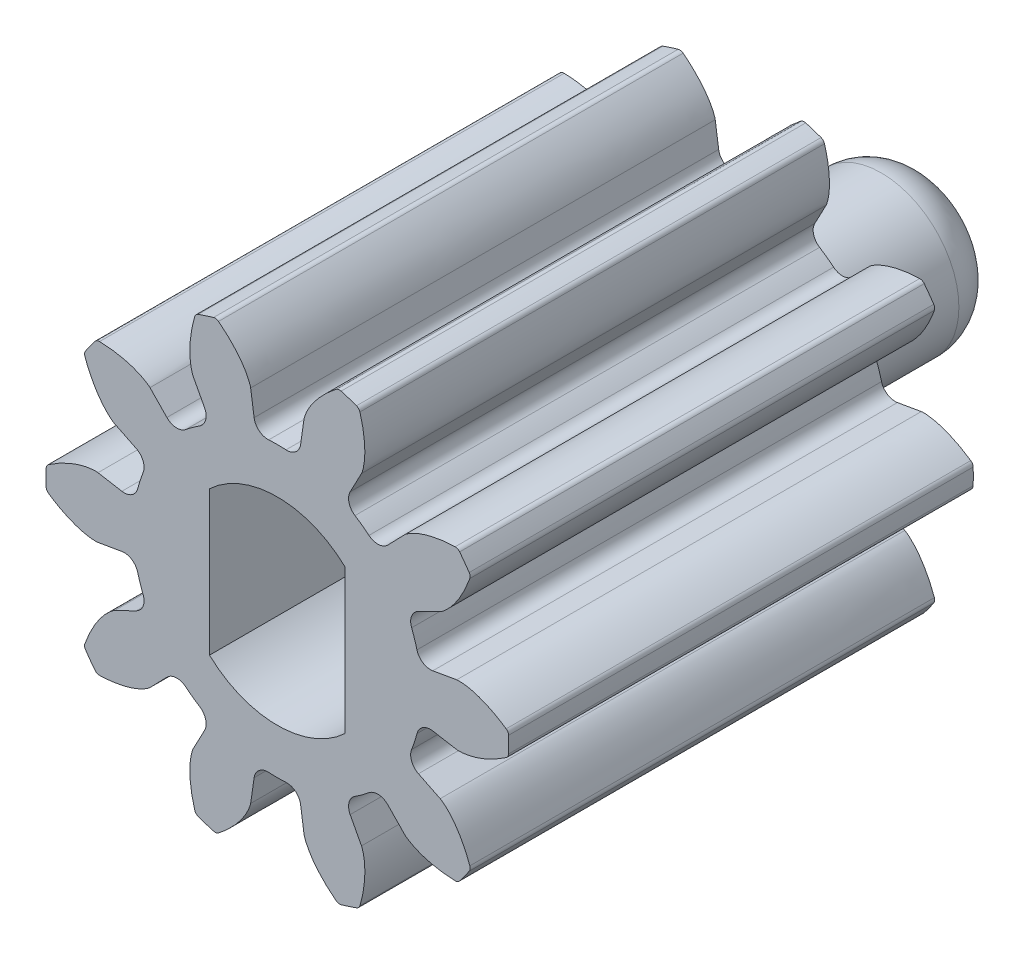
SolidWorks part; units mm, degrees
material "ABS"
ref_plane "Front" through (0, 0, 0) normal (0, 0, 1) x (1, 0, 0)
ref_plane "Top" through (0, 0, 0) normal (0, 1, 0) x (1, 0, 0)
ref_plane "Right" through (0, 0, 0) normal (1, 0, 0) x (0, 0, -1)
sketch "Sketch1" plane through (0, 0, 0) normal (0, 0, 1) x (1, 0, 0)
  circle A0 centre (0, 0) radius 6.35
  dimension "OutsideDiameter" = 12.7
extrude "Boss-Extrude1" add sketch "Sketch1" along normal blind 12.7
sketch "Sketch3" plane through (0, 0, 0) normal (0, 0, 1) x (1, 0, 0)
  line L0 (0, 0) -> (43.7181, 0) construction
  line L2 (0, 0) -> (-0.5624, 3.9287) construction
  line L3 (0, 0) -> (0.5624, 3.9287) construction
  line L4 (0.5624, 3.9287) -> (0.7046, 4.9224) construction
  line L5 (0, 0) -> (0, 61.276) construction
  line L6 (-0.5624, 3.9287) -> (-0.7046, 4.9224) construction
  circle A0 centre (0, 0) radius 6.35 construction
  circle A1 centre (0, 0) radius 5.2917 construction
  circle A2 centre (0, 0) radius 4.9725 construction
  arc A3 (0.5624, 3.9287) -> (-0.5624, 3.9287) centre (0, 0) ccw construction
  arc A5 (1.6642, 6.128) -> (-1.6642, 6.128) centre (0, 0) ccw
  spline S0 degree 4 poles (-0.7046, 4.9224) (-0.705, 4.9247) (-0.7061, 4.9311) (-0.7087, 4.9431) (-0.7137, 4.9626) (-0.721, 4.9872) (-0.7316, 5.0187) (-0.7454, 5.0554) (-0.7621, 5.0953) (-0.7818, 5.1381) (-0.8028, 5.1804) (-0.825, 5.2221) (-0.8483, 5.2631) (-0.8779, 5.3122) (-0.9151, 5.3703) (-0.9613, 5.437) (-1.0167, 5.511) (-1.0764, 5.5846) (-1.1378, 5.6556) (-1.2027, 5.7255) (-1.2676, 5.7919) (-1.338, 5.8588) (-1.4044, 5.9196) (-1.4819, 5.9855) (-1.5453, 6.0379) (-1.6323, 6.1046) (-1.6846, 6.1433) (-1.7469, 6.1876) (-1.7752, 6.2068) (-1.7925, 6.2186) knots 0 0 0 0 0 0.005377 0.015084 0.028532 0.04661 0.064855 0.092111 0.119476 0.146842 0.174209 0.201575 0.228941 0.256307 0.307035 0.361767 0.4165 0.471232 0.525964 0.580697 0.635429 0.690161 0.744894 0.799626 0.854358 0.909091 0.954545 1 1 1 1 1 construction
  spline S1 degree 4 poles (-0.7046, 4.9224) (-0.705, 4.9247) (-0.7061, 4.9311) (-0.7087, 4.9431) (-0.7137, 4.9626) (-0.721, 4.9872) (-0.7316, 5.0187) (-0.7454, 5.0554) (-0.7621, 5.0953) (-0.7818, 5.1381) (-0.8028, 5.1804) (-0.825, 5.2221) (-0.8483, 5.2631) (-0.8779, 5.3122) (-0.9151, 5.3703) (-0.9613, 5.437) (-1.0167, 5.511) (-1.0764, 5.5846) (-1.1378, 5.6556) (-1.2027, 5.7255) (-1.2676, 5.7919) (-1.338, 5.8588) (-1.4044, 5.9196) (-1.4819, 5.9855) (-1.5453, 6.0379) (-1.6134, 6.0902) (-1.647, 6.1153) (-1.6642, 6.128) knots 0 0 0 0 0 0.005377 0.015084 0.028532 0.04661 0.064855 0.092111 0.119476 0.146842 0.174209 0.201575 0.228941 0.256307 0.307035 0.361767 0.4165 0.471232 0.525964 0.580697 0.635429 0.690161 0.744894 0.799626 0.854358 0.909091 0.909091 0.909091 0.909091 0.909091
  spline S2 degree 4 poles (0.7046, 4.9224) (0.705, 4.9247) (0.7061, 4.9311) (0.7087, 4.9431) (0.7137, 4.9626) (0.721, 4.9872) (0.7316, 5.0187) (0.7454, 5.0554) (0.7621, 5.0953) (0.7818, 5.1381) (0.8028, 5.1804) (0.825, 5.2221) (0.8483, 5.2631) (0.8779, 5.3122) (0.9151, 5.3703) (0.9613, 5.437) (1.0167, 5.511) (1.0764, 5.5846) (1.1378, 5.6556) (1.2027, 5.7255) (1.2676, 5.7919) (1.338, 5.8588) (1.4044, 5.9196) (1.4819, 5.9855) (1.5453, 6.0379) (1.6323, 6.1046) (1.6846, 6.1433) (1.7469, 6.1876) (1.7752, 6.2068) (1.7925, 6.2186) knots 0 0 0 0 0 0.005377 0.015084 0.028532 0.04661 0.064855 0.092111 0.119476 0.146842 0.174209 0.201575 0.228941 0.256307 0.307035 0.361767 0.4165 0.471232 0.525964 0.580697 0.635429 0.690161 0.744894 0.799626 0.854358 0.909091 0.954545 1 1 1 1 1 construction
  spline S3 degree 4 poles (0.7046, 4.9224) (0.705, 4.9247) (0.7061, 4.9311) (0.7087, 4.9431) (0.7137, 4.9626) (0.721, 4.9872) (0.7316, 5.0187) (0.7454, 5.0554) (0.7621, 5.0953) (0.7818, 5.1381) (0.8028, 5.1804) (0.825, 5.2221) (0.8483, 5.2631) (0.8779, 5.3122) (0.9151, 5.3703) (0.9613, 5.437) (1.0167, 5.511) (1.0764, 5.5846) (1.1378, 5.6556) (1.2027, 5.7255) (1.2676, 5.7919) (1.338, 5.8588) (1.4044, 5.9196) (1.4819, 5.9855) (1.5453, 6.0379) (1.6134, 6.0902) (1.647, 6.1153) (1.6642, 6.128) knots 0 0 0 0 0 0.005377 0.015084 0.028532 0.04661 0.064855 0.092111 0.119476 0.146842 0.174209 0.201575 0.228941 0.256307 0.307035 0.361767 0.4165 0.471232 0.525964 0.580697 0.635429 0.690161 0.744894 0.799626 0.854358 0.909091 0.909091 0.909091 0.909091 0.909091
  point P0 (0, 3.9688)
  dimension "OutsideDiameter" = 12.7
  dimension "PitchCircle" = 10.5833
  dimension "BaseCircle" = 9.9451
  dimension "DedendumCircle" = 7.9375
sketch "DCLTBC" plane through (0, 0, 0) normal (0, 0, 1) x (1, 0, 0)
  line L0 (0, 0) -> (41.04, 0) construction
  line L1 (-0.5624, 3.9287) -> (-0.7046, 4.9224) construction
  line L2 (0.5624, 3.9287) -> (0.7046, 4.9224) construction
  line L3 (-0.5624, 3.9287) -> (-0.7046, 4.9224)
  line L4 (0.5624, 3.9287) -> (0.7046, 4.9224)
  line L5 (0, 0) -> (0, 104.9356) construction
  circle A0 centre (0, 0) radius 6.35
  circle A1 centre (0, 0) radius 5.2917 construction
  circle A2 centre (0, 0) radius 4.9725 construction
  arc A3 (0.5624, 3.9287) -> (-0.5624, 3.9287) centre (0, 0) ccw construction
  arc A4 (0.5624, 3.9287) -> (-0.5624, 3.9287) centre (0, 0) ccw
  spline S0 degree 4 poles (-988.7588, -149.038) (-11.8151, 2.4708) (-0.7866, 4.3496) (-0.6413, 4.6789) (-0.7137, 4.9626) (-0.721, 4.9872) (-0.7316, 5.0187) (-0.7454, 5.0554) (-0.7621, 5.0953) (-0.7818, 5.1381) (-0.8028, 5.1804) (-0.825, 5.2221) (-0.8483, 5.2631) (-0.8779, 5.3122) (-0.9151, 5.3703) (-0.9613, 5.437) (-1.0167, 5.511) (-1.0764, 5.5846) (-1.1378, 5.6556) (-1.2027, 5.7255) (-1.2676, 5.7919) (-1.338, 5.8588) (-1.4044, 5.9196) (-1.4819, 5.9855) (-1.8387, 6.2805) (-3.231, 7.2231) (17.05, -7.85) (-807.2758, 598.5552) knots -0.632257 -0.632257 -0.632257 -0.632257 -0.632257 0.005377 0.015084 0.028532 0.04661 0.064855 0.092111 0.119476 0.146842 0.174209 0.201575 0.228941 0.256307 0.307035 0.361767 0.4165 0.471232 0.525964 0.580697 0.635429 0.690161 0.744894 0.799626 0.854358 1.920904 1.920904 1.920904 1.920904 1.920904 only from (-0.7046, 4.9224) to (-1.6642, 6.128) construction
  spline S1 degree 4 poles (988.7588, -149.038) (11.8151, 2.4708) (0.7866, 4.3496) (0.6413, 4.6789) (0.7137, 4.9626) (0.721, 4.9872) (0.7316, 5.0187) (0.7454, 5.0554) (0.7621, 5.0953) (0.7818, 5.1381) (0.8028, 5.1804) (0.825, 5.2221) (0.8483, 5.2631) (0.8779, 5.3122) (0.9151, 5.3703) (0.9613, 5.437) (1.0167, 5.511) (1.0764, 5.5846) (1.1378, 5.6556) (1.2027, 5.7255) (1.2676, 5.7919) (1.338, 5.8588) (1.4044, 5.9196) (1.4819, 5.9855) (1.8387, 6.2805) (3.231, 7.2231) (-17.05, -7.85) (807.2758, 598.5552) knots -0.632257 -0.632257 -0.632257 -0.632257 -0.632257 0.005377 0.015084 0.028532 0.04661 0.064855 0.092111 0.119476 0.146842 0.174209 0.201575 0.228941 0.256307 0.307035 0.361767 0.4165 0.471232 0.525964 0.580697 0.635429 0.690161 0.744894 0.799626 0.854358 1.920904 1.920904 1.920904 1.920904 1.920904 only from (0.7046, 4.9224) to (1.6642, 6.128) construction
  spline S2 degree 4 poles (-0.7046, 4.9224) (-0.705, 4.9247) (-0.7061, 4.9311) (-0.7087, 4.9431) (-0.7137, 4.9626) (-0.721, 4.9872) (-0.7316, 5.0187) (-0.7454, 5.0554) (-0.7621, 5.0953) (-0.7818, 5.1381) (-0.8028, 5.1804) (-0.825, 5.2221) (-0.8483, 5.2631) (-0.8779, 5.3122) (-0.9151, 5.3703) (-0.9613, 5.437) (-1.0167, 5.511) (-1.0764, 5.5846) (-1.1378, 5.6556) (-1.2027, 5.7255) (-1.2676, 5.7919) (-1.338, 5.8588) (-1.4044, 5.9196) (-1.4819, 5.9855) (-1.5453, 6.0379) (-1.6134, 6.0902) (-1.647, 6.1153) (-1.6642, 6.128) knots 0 0 0 0 0 0.005377 0.015084 0.028532 0.04661 0.064855 0.092111 0.119476 0.146842 0.174209 0.201575 0.228941 0.256307 0.307035 0.361767 0.4165 0.471232 0.525964 0.580697 0.635429 0.690161 0.744894 0.799626 0.854358 0.909091 0.909091 0.909091 0.909091 0.909091
  spline S3 degree 4 poles (0.7046, 4.9224) (0.705, 4.9247) (0.7061, 4.9311) (0.7087, 4.9431) (0.7137, 4.9626) (0.721, 4.9872) (0.7316, 5.0187) (0.7454, 5.0554) (0.7621, 5.0953) (0.7818, 5.1381) (0.8028, 5.1804) (0.825, 5.2221) (0.8483, 5.2631) (0.8779, 5.3122) (0.9151, 5.3703) (0.9613, 5.437) (1.0167, 5.511) (1.0764, 5.5846) (1.1378, 5.6556) (1.2027, 5.7255) (1.2676, 5.7919) (1.338, 5.8588) (1.4044, 5.9196) (1.4819, 5.9855) (1.5453, 6.0379) (1.6134, 6.0902) (1.647, 6.1153) (1.6642, 6.128) knots 0 0 0 0 0 0.005377 0.015084 0.028532 0.04661 0.064855 0.092111 0.119476 0.146842 0.174209 0.201575 0.228941 0.256307 0.307035 0.361767 0.4165 0.471232 0.525964 0.580697 0.635429 0.690161 0.744894 0.799626 0.854358 0.909091 0.909091 0.909091 0.909091 0.909091
  dimension "OutsideDiameter" = 12.7
  dimension "PitchCircle" = 10.5833
  dimension "BaseCircle" = 9.9451
extrude "Cut-Extrude-DCLTBC" cut sketch "DCLTBC" along normal through all contours L4 S3 A0 S2 L3 A4 region at (0, 5.3543, 0)
fillet "Fillet-Tip-DCLTBC" radius 0.1775 2 edges at (1.6642, 6.128, 6.35) (-1.6642, 6.128, 6.35)
fillet "Fillet-Root-DCLTBC" radius 0.3551 2 edges at (-0.5624, 3.9287, 6.35) (0.5624, 3.9287, 6.35)
pattern_circular "CirPattern-DCLTBC" count 10 over 360 about axis through (0, 0, 12.7) along (0, 0, 1) of "Cut-Extrude-DCLTBC", "Fillet-Tip-DCLTBC", "Fillet-Root-DCLTBC"
sketch "DCGTBC" [suppressed] plane through (0, 0, 0) normal (0, 0, 1) x (1, 0, 0)
  line L0 (0, 0) -> (41.04, 0) construction
  line L1 (-22.6634, 1.9828) -> (0, 0) construction
  line L2 (0, 0) -> (22.6634, 1.9828) construction
  line L3 (0, 0) -> (-16.5124, 0)
  line L5 (0, 0) -> (0, 104.9356) construction
  circle A0 centre (0, 0) radius 25
  circle A1 centre (0, 0) radius 24 construction
  circle A2 centre (0, 0) radius 21.7514 construction
  arc A3 (0.0626, 22.7499) -> (-0.0626, 22.7499) centre (0, 0) ccw construction
  arc A11 (22.6634, 1.9828) -> (-22.6634, 1.9828) centre (0, 0) ccw
  spline S4 degree 4 poles (999.7589, -2.0808) (12.8658, 20.0937) (0.2547, 20.6746) (0.0189, 21.2606) (0.0654, 21.8429) (0.0715, 21.8997) (0.0812, 21.973) (0.095, 22.0592) (0.1126, 22.1539) (0.1343, 22.2566) (0.1583, 22.3589) (0.1845, 22.4607) (0.2124, 22.562) (0.2486, 22.6844) (0.2952, 22.8308) (0.3543, 23.0013) (0.4268, 23.1939) (0.5065, 23.3893) (0.5897, 23.5809) (0.6793, 23.7735) (0.7698, 23.9592) (0.8695, 24.151) (0.9643, 24.3275) (1.0767, 24.524) (1.517, 25.277) (3.0654, 27.5692) (-13.787, 0.9944) (540.7091, 867.0187) knots -0.561807 -0.561807 -0.561807 -0.561807 -0.561807 0.005377 0.015084 0.028532 0.04661 0.064855 0.092111 0.119476 0.146842 0.174209 0.201575 0.228941 0.256307 0.307035 0.361767 0.4165 0.471232 0.525964 0.580697 0.635429 0.690161 0.744894 0.799626 0.854358 1.731906 1.731906 1.731906 1.731906 1.731906 only from (0.0598, 21.7513) to (1.3455, 24.9638) construction
  spline S5 degree 4 poles (-999.7589, -2.0808) (-12.8658, 20.0937) (-0.2547, 20.6746) (-0.0189, 21.2606) (-0.0654, 21.8429) (-0.0715, 21.8997) (-0.0812, 21.973) (-0.095, 22.0592) (-0.1126, 22.1539) (-0.1343, 22.2566) (-0.1583, 22.3589) (-0.1845, 22.4607) (-0.2124, 22.562) (-0.2486, 22.6844) (-0.2952, 22.8308) (-0.3543, 23.0013) (-0.4268, 23.1939) (-0.5065, 23.3893) (-0.5897, 23.5809) (-0.6793, 23.7735) (-0.7698, 23.9592) (-0.8695, 24.151) (-0.9643, 24.3275) (-1.0767, 24.524) (-1.517, 25.277) (-3.0654, 27.5692) (13.787, 0.9944) (-540.7091, 867.0187) knots -0.561807 -0.561807 -0.561807 -0.561807 -0.561807 0.005377 0.015084 0.028532 0.04661 0.064855 0.092111 0.119476 0.146842 0.174209 0.201575 0.228941 0.256307 0.307035 0.361767 0.4165 0.471232 0.525964 0.580697 0.635429 0.690161 0.744894 0.799626 0.854358 1.731906 1.731906 1.731906 1.731906 1.731906 only from (-0.0598, 21.7513) to (-1.3455, 24.9638) construction
  spline S6 degree 4 poles (0.0598, 21.7513) (0.0599, 21.7565) (0.0603, 21.7709) (0.0618, 21.7983) (0.0654, 21.8429) (0.0715, 21.8997) (0.0812, 21.973) (0.095, 22.0592) (0.1126, 22.1539) (0.1343, 22.2566) (0.1583, 22.3589) (0.1845, 22.4607) (0.2124, 22.562) (0.2486, 22.6844) (0.2952, 22.8308) (0.3543, 23.0013) (0.4268, 23.1939) (0.5065, 23.3893) (0.5897, 23.5809) (0.6793, 23.7735) (0.7698, 23.9592) (0.8695, 24.151) (0.9643, 24.3275) (1.0767, 24.524) (1.1693, 24.6823) (1.27, 24.8447) (1.3197, 24.9235) (1.3455, 24.9638) knots 0 0 0 0 0 0.005377 0.015084 0.028532 0.04661 0.064855 0.092111 0.119476 0.146842 0.174209 0.201575 0.228941 0.256307 0.307035 0.361767 0.4165 0.471232 0.525964 0.580697 0.635429 0.690161 0.744894 0.799626 0.854358 0.909091 0.909091 0.909091 0.909091 0.909091
  spline S7 degree 4 poles (-0.0598, 21.7513) (-0.0599, 21.7565) (-0.0603, 21.7709) (-0.0618, 21.7983) (-0.0654, 21.8429) (-0.0715, 21.8997) (-0.0812, 21.973) (-0.095, 22.0592) (-0.1126, 22.1539) (-0.1343, 22.2566) (-0.1583, 22.3589) (-0.1845, 22.4607) (-0.2124, 22.562) (-0.2486, 22.6844) (-0.2952, 22.8308) (-0.3543, 23.0013) (-0.4268, 23.1939) (-0.5065, 23.3893) (-0.5897, 23.5809) (-0.6793, 23.7735) (-0.7698, 23.9592) (-0.8695, 24.151) (-0.9643, 24.3275) (-1.0767, 24.524) (-1.1693, 24.6823) (-1.27, 24.8447) (-1.3197, 24.9235) (-1.3455, 24.9638) knots 0 0 0 0 0 0.005377 0.015084 0.028532 0.04661 0.064855 0.092111 0.119476 0.146842 0.174209 0.201575 0.228941 0.256307 0.307035 0.361767 0.4165 0.471232 0.525964 0.580697 0.635429 0.690161 0.744894 0.799626 0.854358 0.909091 0.909091 0.909091 0.909091 0.909091
  dimension "D1" = 5
  dimension "D2" = 5
  dimension "OutsideDiameter" = 12.7
  dimension "PitchCircle" = 10.5833
  dimension "BaseCircle" = 9.9451
extrude "Cut-Extrude-DCGTBC" [suppressed] cut sketch "DCGTBC" along normal through all
fillet "Fillet-Tip-DCGTBC" [suppressed] radius 0.1775
pattern_circular "CirPattern-DCGTBC" [suppressed] count 10 over 360 of bodies 112
sketch "Sketch4" plane through (0, 0, 12.7) normal (0, 0, 1) x (1, 0, 0)
  circle A1 centre (0, 0) radius 2.7051
  dimension "D1" = 5.4102
extrude "Cut-Extrude2" cut sketch "Sketch4" against normal through all
sketch "Sketch5" plane through (0, 0, 12.7) normal (0, 0, 1) x (1, 0, 0)
  line L0 (-1.8542, 1.9696) -> (-1.8542, -1.9696)
  line L1 (1.8542, 1.9696) -> (1.8542, -1.9696)
  circle A0 centre (0, 0) radius 2.7051 construction
  circle A1 centre (0, 0) radius 2.7051
  dimension "D1" = 3.7084
extrude "Boss-Extrude2" add sketch "Sketch5" against normal through all contours L0 A1 | L1 A1 region at (-2.1996, 0, 12.7) region at (2.1996, 0, 12.7)
sketch "Sketch6" plane through (0, 0, 0) normal (0, 0, -1) x (-1, 0, 0)
  line L2 (-1.8542, 1.9696) -> (-1.8542, -1.9696)
  line L3 (1.8542, -1.9696) -> (1.8542, 1.9696)
  line L4 (-1.8542, 1.9696) -> (-1.8542, -1.9696)
  line L5 (1.8542, -1.9696) -> (1.8542, 1.9696)
  arc A2 (-1.8542, -1.9696) -> (1.8542, -1.9696) centre (0, 0) ccw
  arc A3 (1.8542, 1.9696) -> (-1.8542, 1.9696) centre (0, 0) ccw
  arc A4 (-1.8542, -1.9696) -> (1.8542, -1.9696) centre (0, 0) ccw
  arc A5 (1.8542, 1.9696) -> (-1.8542, 1.9696) centre (0, 0) ccw
  dimension "D1" = 0
extrude "Boss-Extrude3" add sketch "Sketch6" against normal blind 3.175
sketch "Sketch7" plane through (0, 0, 0) normal (0, 0, -1) x (-1, 0, 0)
  circle A0 centre (0, 0) radius 2.1209
  dimension "D1" = 4.2418
extrude "Boss-Extrude4" add sketch "Sketch7" along normal blind 5.08
fillet "Fillet1" radius 1.27 1 edges at (-2.1209, 0, -5.08)
sketch "Sketch8" plane through (0, 0, 12.7) normal (0, 0, 1) x (1, 0, 0)
  line L50 (0.7297, 4.9185) -> (0.6357, 4.2621)
  line L51 (-0.6357, 4.2621) -> (-0.7297, 4.9185)
  line L52 (-2.3007, 4.4081) -> (-1.9909, 3.8218)
  line L53 (-3.0196, 3.0745) -> (-3.4814, 3.5503)
  line L54 (-4.4523, 2.2139) -> (-3.8571, 1.9217)
  line L55 (-4.25, 0.7124) -> (-4.9033, 0.8259)
  line L56 (-4.9033, -0.8259) -> (-4.25, -0.7124)
  line L57 (-3.8571, -1.9217) -> (-4.4523, -2.2139)
  line L58 (-3.4814, -3.5503) -> (-3.0196, -3.0745)
  line L59 (-1.9909, -3.8218) -> (-2.3007, -4.4081)
  line L60 (-0.7297, -4.9185) -> (-0.6357, -4.2621)
  line L61 (0.6357, -4.2621) -> (0.7297, -4.9185)
  line L62 (2.3007, -4.4081) -> (1.9909, -3.8218)
  line L63 (3.0196, -3.0745) -> (3.4814, -3.5503)
  line L64 (4.4523, -2.2139) -> (3.8571, -1.9217)
  line L65 (4.25, -0.7124) -> (4.9033, -0.8259)
  line L66 (4.9033, 0.8259) -> (4.25, 0.7124)
  line L67 (3.8571, 1.9217) -> (4.4523, 2.2139)
  line L68 (3.4814, 3.5503) -> (3.0196, 3.0745)
  line L69 (1.9909, 3.8218) -> (2.3007, 4.4081)
  line L74 (0.7297, 4.9185) -> (0.6357, 4.2621)
  line L75 (-0.6357, 4.2621) -> (-0.7297, 4.9185)
  line L76 (-2.3007, 4.4081) -> (-1.9909, 3.8218)
  line L77 (-3.0196, 3.0745) -> (-3.4814, 3.5503)
  line L78 (-4.4523, 2.2139) -> (-3.8571, 1.9217)
  line L79 (-4.25, 0.7124) -> (-4.9033, 0.8259)
  line L80 (-4.9033, -0.8259) -> (-4.25, -0.7124)
  line L81 (-3.8571, -1.9217) -> (-4.4523, -2.2139)
  line L82 (-3.4814, -3.5503) -> (-3.0196, -3.0745)
  line L83 (-1.9909, -3.8218) -> (-2.3007, -4.4081)
  line L84 (-0.7297, -4.9185) -> (-0.6357, -4.2621)
  line L85 (0.6357, -4.2621) -> (0.7297, -4.9185)
  line L86 (2.3007, -4.4081) -> (1.9909, -3.8218)
  line L87 (3.0196, -3.0745) -> (3.4814, -3.5503)
  line L88 (4.4523, -2.2139) -> (3.8571, -1.9217)
  line L89 (4.25, -0.7124) -> (4.9033, -0.8259)
  line L90 (4.9033, 0.8259) -> (4.25, 0.7124)
  line L91 (3.8571, 1.9217) -> (4.4523, 2.2139)
  line L92 (3.4814, 3.5503) -> (3.0196, 3.0745)
  line L93 (1.9909, 3.8218) -> (2.3007, 4.4081)
  arc A150 (2.1634, 5.9431) -> (1.743, 6.0797) centre (0, 0) ccw
  arc A151 (1.743, 6.0797) -> (1.6082, 6.054) centre (1.7011, 5.9334) ccw
  arc A152 (0.2363, 3.9363) -> (0.6357, 4.2621) centre (0.2591, 4.3161) ccw
  arc A153 (0.2363, 3.9363) -> (-0.2363, 3.9363) centre (0, 0) ccw
  arc A154 (-0.6357, 4.2621) -> (-0.2363, 3.9363) centre (-0.2591, 4.3161) ccw
  arc A155 (-1.6082, 6.054) -> (-1.743, 6.0797) centre (-1.7011, 5.9334) ccw
  arc A156 (-1.743, 6.0797) -> (-2.1634, 5.9431) centre (0, 0) ccw
  arc A157 (-2.1634, 5.9431) -> (-2.2573, 5.8431) centre (-2.1114, 5.8001) ccw
  arc A158 (-2.1225, 3.3234) -> (-1.9909, 3.8218) centre (-2.3273, 3.6441) ccw
  arc A159 (-2.1225, 3.3234) -> (-2.5049, 3.0456) centre (0, 0) ccw
  arc A160 (-3.0196, 3.0745) -> (-2.5049, 3.0456) centre (-2.7465, 3.3395) ccw
  arc A161 (-4.8595, 3.9525) -> (-4.9837, 3.894) centre (-4.8638, 3.8004) ccw
  arc A162 (-4.9837, 3.894) -> (-5.2435, 3.5364) centre (0, 0) ccw
  arc A163 (-5.2435, 3.5364) -> (-5.2607, 3.4003) centre (-5.1174, 3.4514) ccw
  arc A164 (-3.6706, 1.4411) -> (-3.8571, 1.9217) centre (-4.0247, 1.5802) ccw
  arc A165 (-3.6706, 1.4411) -> (-3.8166, 0.9916) centre (0, 0) ccw
  arc A166 (-4.25, 0.7124) -> (-3.8166, 0.9916) centre (-4.1849, 1.0873) ccw
  arc A167 (-6.2546, 0.3412) -> (-6.3207, 0.221) centre (-6.1687, 0.2157) ccw
  arc A168 (-6.3207, 0.221) -> (-6.3207, -0.221) centre (0, 0) ccw
  arc A169 (-6.3207, -0.221) -> (-6.2546, -0.3412) centre (-6.1687, -0.2157) ccw
  arc A170 (-3.8166, -0.9916) -> (-4.25, -0.7124) centre (-4.1849, -1.0873) ccw
  arc A171 (-3.8166, -0.9916) -> (-3.6706, -1.4411) centre (0, 0) ccw
  arc A172 (-3.8571, -1.9217) -> (-3.6706, -1.4411) centre (-4.0247, -1.5802) ccw
  arc A173 (-5.2607, -3.4003) -> (-5.2435, -3.5364) centre (-5.1174, -3.4514) ccw
  arc A174 (-5.2435, -3.5364) -> (-4.9837, -3.894) centre (0, 0) ccw
  arc A175 (-4.9837, -3.894) -> (-4.8595, -3.9525) centre (-4.8638, -3.8004) ccw
  arc A176 (-2.5049, -3.0456) -> (-3.0196, -3.0745) centre (-2.7465, -3.3395) ccw
  arc A177 (-2.5049, -3.0456) -> (-2.1225, -3.3234) centre (0, 0) ccw
  arc A178 (-1.9909, -3.8218) -> (-2.1225, -3.3234) centre (-2.3273, -3.6441) ccw
  arc A179 (-2.2573, -5.8431) -> (-2.1634, -5.9431) centre (-2.1114, -5.8001) ccw
  arc A180 (-2.1634, -5.9431) -> (-1.743, -6.0797) centre (0, 0) ccw
  arc A181 (-1.743, -6.0797) -> (-1.6082, -6.054) centre (-1.7011, -5.9334) ccw
  arc A182 (-0.2363, -3.9363) -> (-0.6357, -4.2621) centre (-0.2591, -4.3161) ccw
  arc A183 (-0.2363, -3.9363) -> (0.2363, -3.9363) centre (0, 0) ccw
  arc A184 (0.6357, -4.2621) -> (0.2363, -3.9363) centre (0.2591, -4.3161) ccw
  arc A185 (1.6082, -6.054) -> (1.743, -6.0797) centre (1.7011, -5.9334) ccw
  arc A186 (1.743, -6.0797) -> (2.1634, -5.9431) centre (0, 0) ccw
  arc A187 (2.1634, -5.9431) -> (2.2573, -5.8431) centre (2.1114, -5.8001) ccw
  arc A188 (2.1225, -3.3234) -> (1.9909, -3.8218) centre (2.3273, -3.6441) ccw
  arc A189 (2.1225, -3.3234) -> (2.5049, -3.0456) centre (0, 0) ccw
  arc A190 (3.0196, -3.0745) -> (2.5049, -3.0456) centre (2.7465, -3.3395) ccw
  arc A191 (4.8595, -3.9525) -> (4.9837, -3.894) centre (4.8638, -3.8004) ccw
  arc A192 (4.9837, -3.894) -> (5.2435, -3.5364) centre (0, 0) ccw
  arc A193 (5.2435, -3.5364) -> (5.2607, -3.4003) centre (5.1174, -3.4514) ccw
  arc A194 (3.6706, -1.4411) -> (3.8571, -1.9217) centre (4.0247, -1.5802) ccw
  arc A195 (3.6706, -1.4411) -> (3.8166, -0.9916) centre (0, 0) ccw
  arc A196 (4.25, -0.7124) -> (3.8166, -0.9916) centre (4.1849, -1.0873) ccw
  arc A197 (6.2546, -0.3412) -> (6.3207, -0.221) centre (6.1687, -0.2157) ccw
  arc A198 (6.3207, -0.221) -> (6.3207, 0.221) centre (0, 0) ccw
  arc A199 (6.3207, 0.221) -> (6.2546, 0.3412) centre (6.1687, 0.2157) ccw
  arc A200 (3.8166, 0.9916) -> (4.25, 0.7124) centre (4.1849, 1.0873) ccw
  arc A201 (3.8166, 0.9916) -> (3.6706, 1.4411) centre (0, 0) ccw
  arc A202 (3.8571, 1.9217) -> (3.6706, 1.4411) centre (4.0247, 1.5802) ccw
  arc A203 (5.2607, 3.4003) -> (5.2435, 3.5364) centre (5.1174, 3.4514) ccw
  arc A204 (5.2435, 3.5364) -> (4.9837, 3.894) centre (0, 0) ccw
  arc A205 (4.9837, 3.894) -> (4.8595, 3.9525) centre (4.8638, 3.8004) ccw
  arc A206 (2.5049, 3.0456) -> (3.0196, 3.0745) centre (2.7465, 3.3395) ccw
  arc A207 (2.5049, 3.0456) -> (2.1225, 3.3234) centre (0, 0) ccw
  arc A208 (1.9909, 3.8218) -> (2.1225, 3.3234) centre (2.3273, 3.6441) ccw
  arc A209 (2.2573, 5.8431) -> (2.1634, 5.9431) centre (2.1114, 5.8001) ccw
  arc A222 (2.1634, 5.9431) -> (1.743, 6.0797) centre (0, 0) ccw
  arc A223 (1.743, 6.0797) -> (1.6082, 6.054) centre (1.7011, 5.9334) ccw
  arc A224 (0.2363, 3.9363) -> (0.6357, 4.2621) centre (0.2591, 4.3161) ccw
  arc A225 (0.2363, 3.9363) -> (-0.2363, 3.9363) centre (0, 0) ccw
  arc A226 (-0.6357, 4.2621) -> (-0.2363, 3.9363) centre (-0.2591, 4.3161) ccw
  arc A227 (-1.6082, 6.054) -> (-1.743, 6.0797) centre (-1.7011, 5.9334) ccw
  arc A228 (-1.743, 6.0797) -> (-2.1634, 5.9431) centre (0, 0) ccw
  arc A229 (-2.1634, 5.9431) -> (-2.2573, 5.8431) centre (-2.1114, 5.8001) ccw
  arc A230 (-2.1225, 3.3234) -> (-1.9909, 3.8218) centre (-2.3273, 3.6441) ccw
  arc A231 (-2.1225, 3.3234) -> (-2.5049, 3.0456) centre (0, 0) ccw
  arc A232 (-3.0196, 3.0745) -> (-2.5049, 3.0456) centre (-2.7465, 3.3395) ccw
  arc A233 (-4.8595, 3.9525) -> (-4.9837, 3.894) centre (-4.8638, 3.8004) ccw
  arc A234 (-4.9837, 3.894) -> (-5.2435, 3.5364) centre (0, 0) ccw
  arc A235 (-5.2435, 3.5364) -> (-5.2607, 3.4003) centre (-5.1174, 3.4514) ccw
  arc A236 (-3.6706, 1.4411) -> (-3.8571, 1.9217) centre (-4.0247, 1.5802) ccw
  arc A237 (-3.6706, 1.4411) -> (-3.8166, 0.9916) centre (0, 0) ccw
  arc A238 (-4.25, 0.7124) -> (-3.8166, 0.9916) centre (-4.1849, 1.0873) ccw
  arc A239 (-6.2546, 0.3412) -> (-6.3207, 0.221) centre (-6.1687, 0.2157) ccw
  arc A240 (-6.3207, 0.221) -> (-6.3207, -0.221) centre (0, 0) ccw
  arc A241 (-6.3207, -0.221) -> (-6.2546, -0.3412) centre (-6.1687, -0.2157) ccw
  arc A242 (-3.8166, -0.9916) -> (-4.25, -0.7124) centre (-4.1849, -1.0873) ccw
  arc A243 (-3.8166, -0.9916) -> (-3.6706, -1.4411) centre (0, 0) ccw
  arc A244 (-3.8571, -1.9217) -> (-3.6706, -1.4411) centre (-4.0247, -1.5802) ccw
  arc A245 (-5.2607, -3.4003) -> (-5.2435, -3.5364) centre (-5.1174, -3.4514) ccw
  arc A246 (-5.2435, -3.5364) -> (-4.9837, -3.894) centre (0, 0) ccw
  arc A247 (-4.9837, -3.894) -> (-4.8595, -3.9525) centre (-4.8638, -3.8004) ccw
  arc A248 (-2.5049, -3.0456) -> (-3.0196, -3.0745) centre (-2.7465, -3.3395) ccw
  arc A249 (-2.5049, -3.0456) -> (-2.1225, -3.3234) centre (0, 0) ccw
  arc A250 (-1.9909, -3.8218) -> (-2.1225, -3.3234) centre (-2.3273, -3.6441) ccw
  arc A251 (-2.2573, -5.8431) -> (-2.1634, -5.9431) centre (-2.1114, -5.8001) ccw
  arc A252 (-2.1634, -5.9431) -> (-1.743, -6.0797) centre (0, 0) ccw
  arc A253 (-1.743, -6.0797) -> (-1.6082, -6.054) centre (-1.7011, -5.9334) ccw
  arc A254 (-0.2363, -3.9363) -> (-0.6357, -4.2621) centre (-0.2591, -4.3161) ccw
  arc A255 (-0.2363, -3.9363) -> (0.2363, -3.9363) centre (0, 0) ccw
  arc A256 (0.6357, -4.2621) -> (0.2363, -3.9363) centre (0.2591, -4.3161) ccw
  arc A257 (1.6082, -6.054) -> (1.743, -6.0797) centre (1.7011, -5.9334) ccw
  arc A258 (1.743, -6.0797) -> (2.1634, -5.9431) centre (0, 0) ccw
  arc A259 (2.1634, -5.9431) -> (2.2573, -5.8431) centre (2.1114, -5.8001) ccw
  arc A260 (2.1225, -3.3234) -> (1.9909, -3.8218) centre (2.3273, -3.6441) ccw
  arc A261 (2.1225, -3.3234) -> (2.5049, -3.0456) centre (0, 0) ccw
  arc A262 (3.0196, -3.0745) -> (2.5049, -3.0456) centre (2.7465, -3.3395) ccw
  arc A263 (4.8595, -3.9525) -> (4.9837, -3.894) centre (4.8638, -3.8004) ccw
  arc A264 (4.9837, -3.894) -> (5.2435, -3.5364) centre (0, 0) ccw
  arc A265 (5.2435, -3.5364) -> (5.2607, -3.4003) centre (5.1174, -3.4514) ccw
  arc A266 (3.6706, -1.4411) -> (3.8571, -1.9217) centre (4.0247, -1.5802) ccw
  arc A267 (3.6706, -1.4411) -> (3.8166, -0.9916) centre (0, 0) ccw
  arc A268 (4.25, -0.7124) -> (3.8166, -0.9916) centre (4.1849, -1.0873) ccw
  arc A269 (6.2546, -0.3412) -> (6.3207, -0.221) centre (6.1687, -0.2157) ccw
  arc A270 (6.3207, -0.221) -> (6.3207, 0.221) centre (0, 0) ccw
  arc A271 (6.3207, 0.221) -> (6.2546, 0.3412) centre (6.1687, 0.2157) ccw
  arc A272 (3.8166, 0.9916) -> (4.25, 0.7124) centre (4.1849, 1.0873) ccw
  arc A273 (3.8166, 0.9916) -> (3.6706, 1.4411) centre (0, 0) ccw
  arc A274 (3.8571, 1.9217) -> (3.6706, 1.4411) centre (4.0247, 1.5802) ccw
  arc A275 (5.2607, 3.4003) -> (5.2435, 3.5364) centre (5.1174, 3.4514) ccw
  arc A276 (5.2435, 3.5364) -> (4.9837, 3.894) centre (0, 0) ccw
  arc A277 (4.9837, 3.894) -> (4.8595, 3.9525) centre (4.8638, 3.8004) ccw
  arc A278 (2.5049, 3.0456) -> (3.0196, 3.0745) centre (2.7465, 3.3395) ccw
  arc A279 (2.5049, 3.0456) -> (2.1225, 3.3234) centre (0, 0) ccw
  arc A280 (1.9909, 3.8218) -> (2.1225, 3.3234) centre (2.3273, 3.6441) ccw
  arc A281 (2.2573, 5.8431) -> (2.1634, 5.9431) centre (2.1114, 5.8001) ccw
  spline S50 degree 3 poles (-1988.4776, 202.2546) (109.7258, -46.196) (10.4478, 16.9202) (1.005, 5.4571) (0.9336, 5.3577) (0.8415, 5.2008) (0.8133, 5.1471) (0.7762, 5.0638) (0.7647, 5.0354) (-0.0091, 2.8409) (1.3647, 0.0279) (1912.7059, -581.1981) knots -29.840031 -29.840031 -29.840031 -29.840031 0.5 0.5 0.75 0.75 0.875 0.875 0.9375 0.9375 5.639417 5.639417 5.639417 5.639417 only from (1.6082, 6.054) to (0.7297, 4.9185)
  spline S51 degree 3 poles (-1875.9168, -690.2171) (-1.143, 0.0163) (0.003, 2.8608) (-0.7648, 5.0357) (-0.7763, 5.0639) (-0.8136, 5.1477) (-0.8422, 5.202) (-0.9344, 5.359) (-1.005, 5.4571) (-10.0736, 16.469) (-105.6764, -37.7703) (1993.233, -131.9181) knots -4.599788 -4.599788 -4.599788 -4.599788 0.0625 0.0625 0.125 0.125 0.25 0.25 0.5 0.5 29.716724 29.716724 29.716724 29.716724 only from (-0.7297, 4.9185) to (-1.6082, 6.054)
  spline S52 degree 3 poles (-1727.5944, -1005.1704) (115.9233, 27.1219) (-1.493, 19.8298) (-2.3945, 5.0056) (-2.3939, 4.8833) (-2.3761, 4.7021) (-2.3674, 4.6421) (-2.3484, 4.5529) (-2.3411, 4.5232) (-1.6772, 2.293) (1.0876, 0.8248) (1889.0312, 654.0612) knots -29.840031 -29.840031 -29.840031 -29.840031 0.5 0.5 0.75 0.75 0.875 0.875 0.9375 0.9375 5.639417 5.639417 5.639417 5.639417 only from (-2.2573, 5.8431) to (-2.3007, 4.4081)
  spline S53 degree 3 poles (-1111.9491, -1661.0335) (-0.9343, -0.6587) (-1.6791, 2.3162) (-3.5786, 3.6244) (-3.6045, 3.6405) (-3.684, 3.6864) (-3.739, 3.7135) (-3.9059, 3.7863) (-4.0207, 3.8242) (-17.8299, 7.4026) (-63.2932, -92.6718) (1690.0989, 1064.869) knots -4.599788 -4.599788 -4.599788 -4.599788 0.0625 0.0625 0.125 0.125 0.25 0.25 0.5 0.5 29.716724 29.716724 29.716724 29.716724 only from (-3.4814, 3.5503) to (-4.8595, 3.9525)
  spline S54 degree 3 poles (-806.8289, -1828.6545) (77.8421, 90.0801) (-12.8635, 15.1651) (-4.8795, 2.6422) (-4.807, 2.5435) (-4.6862, 2.4075) (-4.6439, 2.364) (-4.5761, 2.303) (-4.5526, 2.2833) (-2.7047, 0.8692) (0.3951, 1.3066) (1143.8108, 1639.4913) knots -29.840031 -29.840031 -29.840031 -29.840031 0.5 0.5 0.75 0.75 0.875 0.875 0.9375 0.9375 5.639417 5.639417 5.639417 5.639417 only from (-5.2607, 3.4003) to (-4.4523, 2.2139)
  spline S55 degree 3 poles (76.7453, -1997.3917) (-0.3687, -1.0821) (-2.7198, 0.8869) (-5.0255, 0.8287) (-5.056, 0.8266) (-5.1472, 0.817) (-5.2077, 0.8065) (-5.3855, 0.7673) (-5.5006, 0.7305) (-18.7759, -4.4913) (3.2659, -112.1759) (741.4045, 1854.9123) knots -4.599788 -4.599788 -4.599788 -4.599788 0.0625 0.0625 0.125 0.125 0.25 0.25 0.5 0.5 29.716724 29.716724 29.716724 29.716724 only from (-4.9033, 0.8259) to (-6.2546, 0.3412)
  spline S56 degree 3 poles (422.1178, -1953.6547) (10.0279, 118.6308) (-19.3206, 4.7078) (-5.5006, -0.7305) (-5.384, -0.7677) (-5.2063, -0.8068) (-5.1465, -0.8171) (-5.0558, -0.8266) (-5.0253, -0.8288) (-2.6991, -0.8865) (-0.4483, 1.2893) (-38.3064, 1998.6915) knots -29.840031 -29.840031 -29.840031 -29.840031 0.5 0.5 0.75 0.75 0.875 0.875 0.9375 0.9375 5.639417 5.639417 5.639417 5.639417 only from (-6.2546, -0.3412) to (-4.9033, -0.8259)
  spline S57 degree 3 poles (1236.1256, -1570.8141) (0.3377, -1.0921) (-2.7217, -0.8812) (-4.5529, -2.2835) (-4.5762, -2.3031) (-4.6444, -2.3645) (-4.6872, -2.4085) (-4.808, -2.5447) (-4.8794, -2.6421) (-12.5501, -14.6697) (68.5775, -88.8325) (-490.4813, 1936.4422) knots -4.599788 -4.599788 -4.599788 -4.599788 0.0625 0.0625 0.125 0.125 0.25 0.25 0.5 0.5 29.716724 29.716724 29.716724 29.716724 only from (-4.4523, -2.2139) to (-5.2607, -3.4003)
  spline S58 degree 3 poles (1489.8299, -1332.4252) (-61.6167, 101.8685) (-18.3979, -7.5477) (-4.0207, -3.8242) (-3.9045, -3.7858) (-3.7377, -3.7129) (-3.6834, -3.6861) (-3.6044, -3.6404) (-3.5784, -3.6242) (-1.6625, -2.3037) (-1.1205, 0.7795) (-1205.7919, 1594.4594) knots -29.840031 -29.840031 -29.840031 -29.840031 0.5 0.5 0.75 0.75 0.875 0.875 0.9375 0.9375 5.639417 5.639417 5.639417 5.639417 only from (-4.8595, -3.9525) to (-3.4814, -3.5503)
  spline S59 degree 3 poles (1923.348, -544.2389) (0.9152, -0.685) (-1.684, -2.3127) (-2.3412, -4.5235) (-2.3485, -4.5531) (-2.3676, -4.6428) (-2.3763, -4.7036) (-2.394, -4.8848) (-2.3945, -5.0056) (-1.5306, -19.2448) (107.6948, -31.5582) (-1535.0199, 1278.317) knots -4.599788 -4.599788 -4.599788 -4.599788 0.0625 0.0625 0.125 0.125 0.25 0.25 0.5 0.5 29.716724 29.716724 29.716724 29.716724 only from (-2.3007, -4.4081) to (-2.2573, -5.8431)
  spline S60 degree 3 poles (1988.4776, -202.2546) (-109.7258, 46.196) (-10.4478, -16.9202) (-1.005, -5.4571) (-0.9336, -5.3577) (-0.8415, -5.2008) (-0.8133, -5.1471) (-0.7762, -5.0638) (-0.7647, -5.0354) (0.0091, -2.8409) (-1.3647, -0.0279) (-1912.7059, 581.1981) knots -29.840031 -29.840031 -29.840031 -29.840031 0.5 0.5 0.75 0.75 0.875 0.875 0.9375 0.9375 5.639417 5.639417 5.639417 5.639417 only from (-1.6082, -6.054) to (-0.7297, -4.9185)
  spline S61 degree 3 poles (1875.9168, 690.2171) (1.143, -0.0163) (-0.003, -2.8608) (0.7648, -5.0357) (0.7763, -5.0639) (0.8136, -5.1477) (0.8422, -5.202) (0.9344, -5.359) (1.005, -5.4571) (10.0736, -16.469) (105.6764, 37.7703) (-1993.233, 131.9181) knots -4.599788 -4.599788 -4.599788 -4.599788 0.0625 0.0625 0.125 0.125 0.25 0.25 0.5 0.5 29.716724 29.716724 29.716724 29.716724 only from (0.7297, -4.9185) to (1.6082, -6.054)
  spline S62 degree 3 poles (1727.5944, 1005.1704) (-115.9233, -27.1219) (1.493, -19.8298) (2.3945, -5.0056) (2.3939, -4.8833) (2.3761, -4.7021) (2.3674, -4.6421) (2.3484, -4.5529) (2.3411, -4.5232) (1.6772, -2.293) (-1.0876, -0.8248) (-1889.0312, -654.0612) knots -29.840031 -29.840031 -29.840031 -29.840031 0.5 0.5 0.75 0.75 0.875 0.875 0.9375 0.9375 5.639417 5.639417 5.639417 5.639417 only from (2.2573, -5.8431) to (2.3007, -4.4081)
  spline S63 degree 3 poles (1111.9491, 1661.0335) (0.9343, 0.6587) (1.6791, -2.3162) (3.5786, -3.6244) (3.6045, -3.6405) (3.684, -3.6864) (3.739, -3.7135) (3.9059, -3.7863) (4.0207, -3.8242) (17.8299, -7.4026) (63.2932, 92.6718) (-1690.0989, -1064.869) knots -4.599788 -4.599788 -4.599788 -4.599788 0.0625 0.0625 0.125 0.125 0.25 0.25 0.5 0.5 29.716724 29.716724 29.716724 29.716724 only from (3.4814, -3.5503) to (4.8595, -3.9525)
  spline S64 degree 3 poles (806.8289, 1828.6545) (-77.8421, -90.0801) (12.8635, -15.1651) (4.8795, -2.6422) (4.807, -2.5435) (4.6862, -2.4075) (4.6439, -2.364) (4.5761, -2.303) (4.5526, -2.2833) (2.7047, -0.8692) (-0.3951, -1.3066) (-1143.8108, -1639.4913) knots -29.840031 -29.840031 -29.840031 -29.840031 0.5 0.5 0.75 0.75 0.875 0.875 0.9375 0.9375 5.639417 5.639417 5.639417 5.639417 only from (5.2607, -3.4003) to (4.4523, -2.2139)
  spline S65 degree 3 poles (-76.7453, 1997.3917) (0.3687, 1.0821) (2.7198, -0.8869) (5.0255, -0.8287) (5.056, -0.8266) (5.1472, -0.817) (5.2077, -0.8065) (5.3855, -0.7673) (5.5006, -0.7305) (18.7759, 4.4913) (-3.2659, 112.1759) (-741.4045, -1854.9123) knots -4.599788 -4.599788 -4.599788 -4.599788 0.0625 0.0625 0.125 0.125 0.25 0.25 0.5 0.5 29.716724 29.716724 29.716724 29.716724 only from (4.9033, -0.8259) to (6.2546, -0.3412)
  spline S66 degree 3 poles (-422.1178, 1953.6547) (-10.0279, -118.6308) (19.3206, -4.7078) (5.5006, 0.7305) (5.384, 0.7677) (5.2063, 0.8068) (5.1465, 0.8171) (5.0558, 0.8266) (5.0253, 0.8288) (2.6991, 0.8865) (0.4483, -1.2893) (38.3064, -1998.6915) knots -29.840031 -29.840031 -29.840031 -29.840031 0.5 0.5 0.75 0.75 0.875 0.875 0.9375 0.9375 5.639417 5.639417 5.639417 5.639417 only from (6.2546, 0.3412) to (4.9033, 0.8259)
  spline S67 degree 3 poles (-1236.1256, 1570.8141) (-0.3377, 1.0921) (2.7217, 0.8812) (4.5529, 2.2835) (4.5762, 2.3031) (4.6444, 2.3645) (4.6872, 2.4085) (4.808, 2.5447) (4.8794, 2.6421) (12.5501, 14.6697) (-68.5775, 88.8325) (490.4813, -1936.4422) knots -4.599788 -4.599788 -4.599788 -4.599788 0.0625 0.0625 0.125 0.125 0.25 0.25 0.5 0.5 29.716724 29.716724 29.716724 29.716724 only from (4.4523, 2.2139) to (5.2607, 3.4003)
  spline S68 degree 3 poles (-1489.8299, 1332.4252) (61.6167, -101.8685) (18.3979, 7.5477) (4.0207, 3.8242) (3.9045, 3.7858) (3.7377, 3.7129) (3.6834, 3.6861) (3.6044, 3.6404) (3.5784, 3.6242) (1.6625, 2.3037) (1.1205, -0.7795) (1205.7919, -1594.4594) knots -29.840031 -29.840031 -29.840031 -29.840031 0.5 0.5 0.75 0.75 0.875 0.875 0.9375 0.9375 5.639417 5.639417 5.639417 5.639417 only from (4.8595, 3.9525) to (3.4814, 3.5503)
  spline S69 degree 3 poles (-1923.348, 544.2389) (-0.9152, 0.685) (1.684, 2.3127) (2.3412, 4.5235) (2.3485, 4.5531) (2.3676, 4.6428) (2.3763, 4.7036) (2.394, 4.8848) (2.3945, 5.0056) (1.5306, 19.2448) (-107.6948, 31.5582) (1535.0199, -1278.317) knots -4.599788 -4.599788 -4.599788 -4.599788 0.0625 0.0625 0.125 0.125 0.25 0.25 0.5 0.5 29.716724 29.716724 29.716724 29.716724 only from (2.3007, 4.4081) to (2.2573, 5.8431)
  spline S74 degree 3 poles (1.6082, 6.054) (1.4153, 5.9053) (1.2365, 5.7382) (1.005, 5.4571) (0.9336, 5.3577) (0.8415, 5.2008) (0.8133, 5.1471) (0.7762, 5.0638) (0.7647, 5.0354) (0.7444, 4.9778) (0.7346, 4.9489) (0.7297, 4.9185) knots 0 0 0 0 0.5 0.5 0.75 0.75 0.875 0.875 0.9375 0.9375 1 1 1 1
  spline S75 degree 3 poles (-0.7297, 4.9185) (-0.7347, 4.9492) (-0.7445, 4.9781) (-0.7648, 5.0357) (-0.7763, 5.0639) (-0.8136, 5.1477) (-0.8422, 5.202) (-0.9344, 5.359) (-1.005, 5.4571) (-1.2358, 5.7374) (-1.4151, 5.9051) (-1.6082, 6.054) knots 0 0 0 0 0.0625 0.0625 0.125 0.125 0.25 0.25 0.5 0.5 1 1 1 1
  spline S76 degree 3 poles (-2.2573, 5.8431) (-2.3261, 5.6094) (-2.3724, 5.3691) (-2.3945, 5.0056) (-2.3939, 4.8833) (-2.3761, 4.7021) (-2.3674, 4.6421) (-2.3484, 4.5529) (-2.3411, 4.5232) (-2.3237, 4.4647) (-2.3146, 4.4356) (-2.3007, 4.4081) knots 0 0 0 0 0.5 0.5 0.75 0.75 0.875 0.875 0.9375 0.9375 1 1 1 1
  spline S77 degree 3 poles (-3.4814, 3.5503) (-3.5034, 3.5722) (-3.5284, 3.5898) (-3.5786, 3.6244) (-3.6045, 3.6405) (-3.684, 3.6864) (-3.739, 3.7135) (-3.9059, 3.7863) (-4.0207, 3.8242) (-4.3721, 3.9152) (-4.6158, 3.9456) (-4.8595, 3.9525) knots 0 0 0 0 0.0625 0.0625 0.125 0.125 0.25 0.25 0.5 0.5 1 1 1 1
  spline S78 degree 3 poles (-5.2607, 3.4003) (-5.1789, 3.1709) (-5.0752, 2.9492) (-4.8795, 2.6422) (-4.807, 2.5435) (-4.6862, 2.4075) (-4.6439, 2.364) (-4.5761, 2.303) (-4.5526, 2.2833) (-4.5042, 2.2462) (-4.4797, 2.228) (-4.4523, 2.2139) knots 0 0 0 0 0.5 0.5 0.75 0.75 0.875 0.875 0.9375 0.9375 1 1 1 1
  spline S79 degree 3 poles (-4.9033, 0.8259) (-4.934, 0.8307) (-4.9645, 0.8303) (-5.0255, 0.8287) (-5.056, 0.8266) (-5.1472, 0.817) (-5.2077, 0.8065) (-5.3855, 0.7673) (-5.5006, 0.7305) (-5.8385, 0.5976) (-6.0534, 0.479) (-6.2546, 0.3412) knots 0 0 0 0 0.0625 0.0625 0.125 0.125 0.25 0.25 0.5 0.5 1 1 1 1
  spline S80 degree 3 poles (-6.2546, -0.3412) (-6.0536, -0.4788) (-5.8394, -0.5972) (-5.5006, -0.7305) (-5.384, -0.7677) (-5.2063, -0.8068) (-5.1465, -0.8171) (-5.0558, -0.8266) (-5.0253, -0.8288) (-4.9642, -0.8303) (-4.9337, -0.8306) (-4.9033, -0.8259) knots 0 0 0 0 0.5 0.5 0.75 0.75 0.875 0.875 0.9375 0.9375 1 1 1 1
  spline S81 degree 3 poles (-4.4523, -2.2139) (-4.48, -2.2281) (-4.5044, -2.2464) (-4.5529, -2.2835) (-4.5762, -2.3031) (-4.6444, -2.3645) (-4.6872, -2.4085) (-4.808, -2.5447) (-4.8794, -2.6421) (-5.0747, -2.9483) (-5.1788, -3.1706) (-5.2607, -3.4003) knots 0 0 0 0 0.0625 0.0625 0.125 0.125 0.25 0.25 0.5 0.5 1 1 1 1
  spline S82 degree 3 poles (-4.8595, -3.9525) (-4.6161, -3.9456) (-4.3732, -3.9155) (-4.0207, -3.8242) (-3.9045, -3.7858) (-3.7377, -3.7129) (-3.6834, -3.6861) (-3.6044, -3.6404) (-3.5784, -3.6242) (-3.5281, -3.5896) (-3.5032, -3.572) (-3.4814, -3.5503) knots 0 0 0 0 0.5 0.5 0.75 0.75 0.875 0.875 0.9375 0.9375 1 1 1 1
  spline S83 degree 3 poles (-2.3007, -4.4081) (-2.3147, -4.4358) (-2.3238, -4.465) (-2.3412, -4.5235) (-2.3485, -4.5531) (-2.3676, -4.6428) (-2.3763, -4.7036) (-2.394, -4.8848) (-2.3945, -5.0056) (-2.3725, -5.368) (-2.3261, -5.6091) (-2.2573, -5.8431) knots 0 0 0 0 0.0625 0.0625 0.125 0.125 0.25 0.25 0.5 0.5 1 1 1 1
  spline S84 degree 3 poles (-1.6082, -6.054) (-1.4153, -5.9053) (-1.2365, -5.7382) (-1.005, -5.4571) (-0.9336, -5.3577) (-0.8415, -5.2008) (-0.8133, -5.1471) (-0.7762, -5.0638) (-0.7647, -5.0354) (-0.7444, -4.9778) (-0.7346, -4.9489) (-0.7297, -4.9185) knots 0 0 0 0 0.5 0.5 0.75 0.75 0.875 0.875 0.9375 0.9375 1 1 1 1
  spline S85 degree 3 poles (0.7297, -4.9185) (0.7347, -4.9492) (0.7445, -4.9781) (0.7648, -5.0357) (0.7763, -5.0639) (0.8136, -5.1477) (0.8422, -5.202) (0.9344, -5.359) (1.005, -5.4571) (1.2358, -5.7374) (1.4151, -5.9051) (1.6082, -6.054) knots 0 0 0 0 0.0625 0.0625 0.125 0.125 0.25 0.25 0.5 0.5 1 1 1 1
  spline S86 degree 3 poles (2.2573, -5.8431) (2.3261, -5.6094) (2.3724, -5.3691) (2.3945, -5.0056) (2.3939, -4.8833) (2.3761, -4.7021) (2.3674, -4.6421) (2.3484, -4.5529) (2.3411, -4.5232) (2.3237, -4.4647) (2.3146, -4.4356) (2.3007, -4.4081) knots 0 0 0 0 0.5 0.5 0.75 0.75 0.875 0.875 0.9375 0.9375 1 1 1 1
  spline S87 degree 3 poles (3.4814, -3.5503) (3.5034, -3.5722) (3.5284, -3.5898) (3.5786, -3.6244) (3.6045, -3.6405) (3.684, -3.6864) (3.739, -3.7135) (3.9059, -3.7863) (4.0207, -3.8242) (4.3721, -3.9152) (4.6158, -3.9456) (4.8595, -3.9525) knots 0 0 0 0 0.0625 0.0625 0.125 0.125 0.25 0.25 0.5 0.5 1 1 1 1
  spline S88 degree 3 poles (5.2607, -3.4003) (5.1789, -3.1709) (5.0752, -2.9492) (4.8795, -2.6422) (4.807, -2.5435) (4.6862, -2.4075) (4.6439, -2.364) (4.5761, -2.303) (4.5526, -2.2833) (4.5042, -2.2462) (4.4797, -2.228) (4.4523, -2.2139) knots 0 0 0 0 0.5 0.5 0.75 0.75 0.875 0.875 0.9375 0.9375 1 1 1 1
  spline S89 degree 3 poles (4.9033, -0.8259) (4.934, -0.8307) (4.9645, -0.8303) (5.0255, -0.8287) (5.056, -0.8266) (5.1472, -0.817) (5.2077, -0.8065) (5.3855, -0.7673) (5.5006, -0.7305) (5.8385, -0.5976) (6.0534, -0.479) (6.2546, -0.3412) knots 0 0 0 0 0.0625 0.0625 0.125 0.125 0.25 0.25 0.5 0.5 1 1 1 1
  spline S90 degree 3 poles (6.2546, 0.3412) (6.0536, 0.4788) (5.8394, 0.5972) (5.5006, 0.7305) (5.384, 0.7677) (5.2063, 0.8068) (5.1465, 0.8171) (5.0558, 0.8266) (5.0253, 0.8288) (4.9642, 0.8303) (4.9337, 0.8306) (4.9033, 0.8259) knots 0 0 0 0 0.5 0.5 0.75 0.75 0.875 0.875 0.9375 0.9375 1 1 1 1
  spline S91 degree 3 poles (4.4523, 2.2139) (4.48, 2.2281) (4.5044, 2.2464) (4.5529, 2.2835) (4.5762, 2.3031) (4.6444, 2.3645) (4.6872, 2.4085) (4.808, 2.5447) (4.8794, 2.6421) (5.0747, 2.9483) (5.1788, 3.1706) (5.2607, 3.4003) knots 0 0 0 0 0.0625 0.0625 0.125 0.125 0.25 0.25 0.5 0.5 1 1 1 1
  spline S92 degree 3 poles (4.8595, 3.9525) (4.6161, 3.9456) (4.3732, 3.9155) (4.0207, 3.8242) (3.9045, 3.7858) (3.7377, 3.7129) (3.6834, 3.6861) (3.6044, 3.6404) (3.5784, 3.6242) (3.5281, 3.5896) (3.5032, 3.572) (3.4814, 3.5503) knots 0 0 0 0 0.5 0.5 0.75 0.75 0.875 0.875 0.9375 0.9375 1 1 1 1
  spline S93 degree 3 poles (2.3007, 4.4081) (2.3147, 4.4358) (2.3238, 4.465) (2.3412, 4.5235) (2.3485, 4.5531) (2.3676, 4.6428) (2.3763, 4.7036) (2.394, 4.8848) (2.3945, 5.0056) (2.3725, 5.368) (2.3261, 5.6091) (2.2573, 5.8431) knots 0 0 0 0 0.0625 0.0625 0.125 0.125 0.25 0.25 0.5 0.5 1 1 1 1
  dimension "D1" = 0.0254
extrude "Cut-Extrude3" cut sketch "Sketch8" against normal through all flip side to cut
equation "\"DiametralPitch\"= 24'Diametral Pitch"
equation "\"NumTeeth\"= 10'Number of Teeth"
equation "\"PressureAngle\"= 20deg'Pressure Angle"
equation "\"Addendum\"= 1 / \"DiametralPitch\"'Addendum"
equation "\"Dedendum\"= 1.25 / \"DiametralPitch\"'Dedendum"
equation "\"WorkingDepth\"= 2 / \"DiametralPitch\"'Working Depth - here for REF (Not used in building model)"
equation "\"WholeDepth\"= 2.25 / \"DiametralPitch\"'Whole Depth - here for REF (Not used in building model)"
equation "\"Clearance\"= .25 / \"DiametralPitch\"'Clearance"
equation "\"CircularPitch\"= pi / \"DiametralPitch\"'Circular Pitch - here for REF (Not used in building model)"
equation "\"PitchCircle\"= \"NumTeeth\" / \"DiametralPitch\"'Pitch Circle - or - Pitch Diameter"
equation "\"OutsideDiameter\"= ( \"NumTeeth\" + 2 ) / \"DiametralPitch\"'Outside Diameter"
equation "\"Fillet_Root\"= \"Clearance\" * cos ( \"PressureAngle\" ) * tan ( ( 90 + \"PressureAngle\" ) / 2 ) 'Fillet Root"
equation "\"AddendumCircle\"= \"PitchCircle\" + ( 2 * \"Addendum\" )'Addendum Circle - or - Addendum Diameter"
equation "\"DedendumCircle\"= \"PitchCircle\" - ( 2 * \"Dedendum\" )'Dedendum Circle - or - Dedendum Diameter"
equation "\"BaseCircle\"= \"PitchCircle\" * cos ( \"PressureAngle\" )'Base Circle - Base Diameter"
equation "\"PitchAngle\"= 360deg / \"NumTeeth\"'Pitch Angle"
equation "\"Alpha\"= sqr ( \"PitchCircle\" ^ 2 - \"BaseCircle\" ^ 2 ) / \"BaseCircle\" * 180 / PI - \"PressureAngle\"'Alpha - Used for Calculating Beta"
equation "\"Beta\"= ( \"PitchAngle\" / 4 - ( \"Alpha\" - 90 ) )'Beta - Used in definition of the parameters for the parametric equation driven curve"
equation "\"Gamma\"= ( \"PitchAngle\" / 4 - ( \"Alpha\" + 90 ) )'Gamma - Used in definition of the parameters for the parametric equation driven curve"
equation "\"Phi\"= sqr ( ( \"AddendumCircle\" / 2 ) ^ 2 - ( \"BaseCircle\" / 2 ) ^ 2 ) / ( \"BaseCircle\" / 2 )'Phi - Used in definition of the parameters for the parametric equation driven curve"
equation "\"DCGTBC\"= iif ( \"DedendumCircle\" > \"BaseCircle\" , \"unsuppressed\" , \"suppressed\" )'if Dedendum Circle IS GREATER THAN BaseCircle THEN UnsuppressORSuppress FEATURE"
equation "\"DCLTBC\"= iif ( \"DedendumCircle\" - .002 > \"BaseCircle\" , \"suppressed\" , \"unsuppressed\" )'if Dedendum Circle - .002 IS GREATER THAN BaseCircle THEN SuppressORUnsuppress FEATURE"
equation "\"Cut-Extrude-DCGTBC\"= iif ( \"DedendumCircle\" > \"BaseCircle\" , \"unsuppressed\" , \"suppressed\" )'if Dedendum Circle IS GREATER THAN BaseCircle THEN UnsuppressORSuppress FEATURE"
equation "\"Cut-Extrude-DCLTBC\"= iif ( \"DedendumCircle\" - .002 > \"BaseCircle\" , \"suppressed\" , \"unsuppressed\" )'if Dedendum Circle - .002 IS GREATER THAN BaseCircle THEN SuppressORUnsuppress FEATURE"
equation "\"CirPattern-DCGTBC\"= iif ( \"DedendumCircle\" > \"BaseCircle\" , \"unsuppressed\" , \"suppressed\" )'if Dedendum Circle IS GREATER THAN BaseCircle THEN UnsuppressORSuppress FEATURE"
equation "\"CirPattern-DCLTBC\"= iif ( \"DedendumCircle\" - .002 > \"BaseCircle\" , \"suppressed\" , \"unsuppressed\" )'if Dedendum Circle - .002 IS GREATER THAN BaseCircle THEN SuppressORUnsuppress FEATURE"
equation "\"Fillet-Tip-DCGTBC\"= iif ( \"DedendumCircle\" > \"BaseCircle\" , \"unsuppressed\" , \"suppressed\" )'if Dedendum Circle IS GREATER THAN BaseCircle THEN UnsuppressORSuppress FEATURE"
equation "\"Fillet-Tip-DCLTBC\"= iif ( \"DedendumCircle\" - .002 > \"BaseCircle\" , \"suppressed\" , \"unsuppressed\" )'if Dedendum Circle - .002 IS GREATER THAN BaseCircle THEN SuppressORUnsuppress FEATURE"
equation "\"Fillet-Root-DCLTBC\"= iif ( \"DedendumCircle\" - .002 > \"BaseCircle\" , \"suppressed\" , \"unsuppressed\" )'if Dedendum Circle - .002 IS GREATER THAN BaseCircle THEN SuppressORUnsuppress FEATURE"
equation "\"D1@CirPattern-DCGTBC\"= \"NumTeeth\"'Number of Teeth"
equation "\"D1@CirPattern-DCLTBC\"= \"NumTeeth\"'Number of Teeth"
equation "\"D1@Fillet-Tip-DCGTBC\"= \"Fillet_Root\" / 2 'Tip Rad For Large No of Teeth"
equation "\"D1@Fillet-Tip-DCLTBC\"=\"Fillet_Root\" / 2'Tip Rad For Small No of Teeth"
equation "\"D1@Fillet-Root-DCLTBC\"= \"Fillet_Root\"'Fillet Root"
